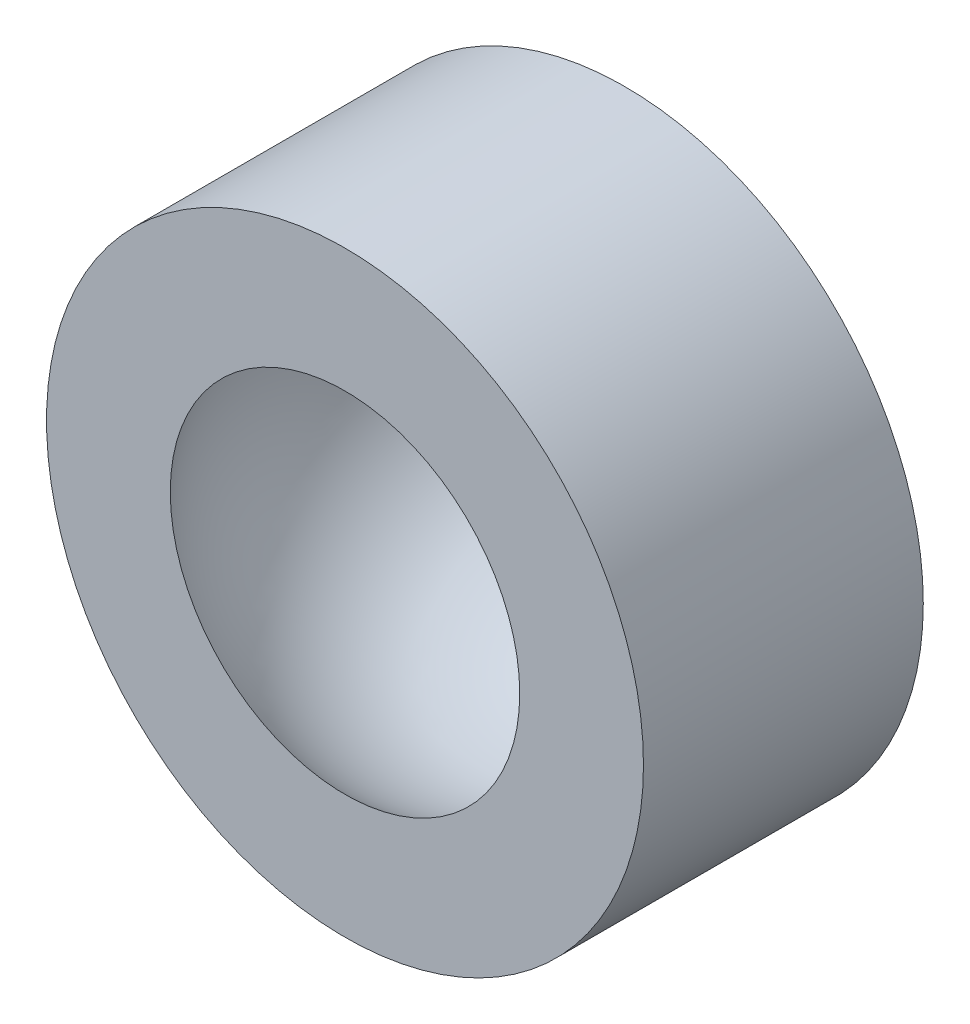
SolidWorks part; units mm, degrees
ref_plane "Front Plane" through (0, 0, 0) normal (0, 0, 1) x (1, 0, 0)
ref_plane "Top Plane" through (0, 0, 0) normal (0, 1, 0) x (1, 0, 0)
ref_plane "Right Plane" through (0, 0, 0) normal (1, 0, 0) x (0, 0, -1)
sketch "Sketch1" plane through (0, 0, 0) normal (0, 0, 1) x (1, 0, 0)
  circle A0 centre (0, 0) radius 2
  circle A1 centre (0, 0) radius 3 construction
  circle A2 centre (0, 0) radius 4
  dimension "D1" = 8
  dimension "D2" = 6
  dimension "D3" = 4
extrude "Boss-Extrude1" add sketch "Sketch1" along normal blind 1.875 and the other way blind 1.875
sketch "Sketch2" plane through (0, 0, 0) normal (0, 0, 1) x (1, 0, 0)
  line L0 (0, 3) -> (0, -3)
  circle A0 centre (0, 0) radius 3 construction
  arc A1 (0, 3) -> (0, -3) centre (0, 0) ccw
revolve "Revolve1" add sketch "Sketch2" angle 360 about L0
combine bodies "Combine1" operation type subtract main body 101 bodies to subtract 102
scale "Scale1" scale about centroid uniform scaling yes scale factor 18
